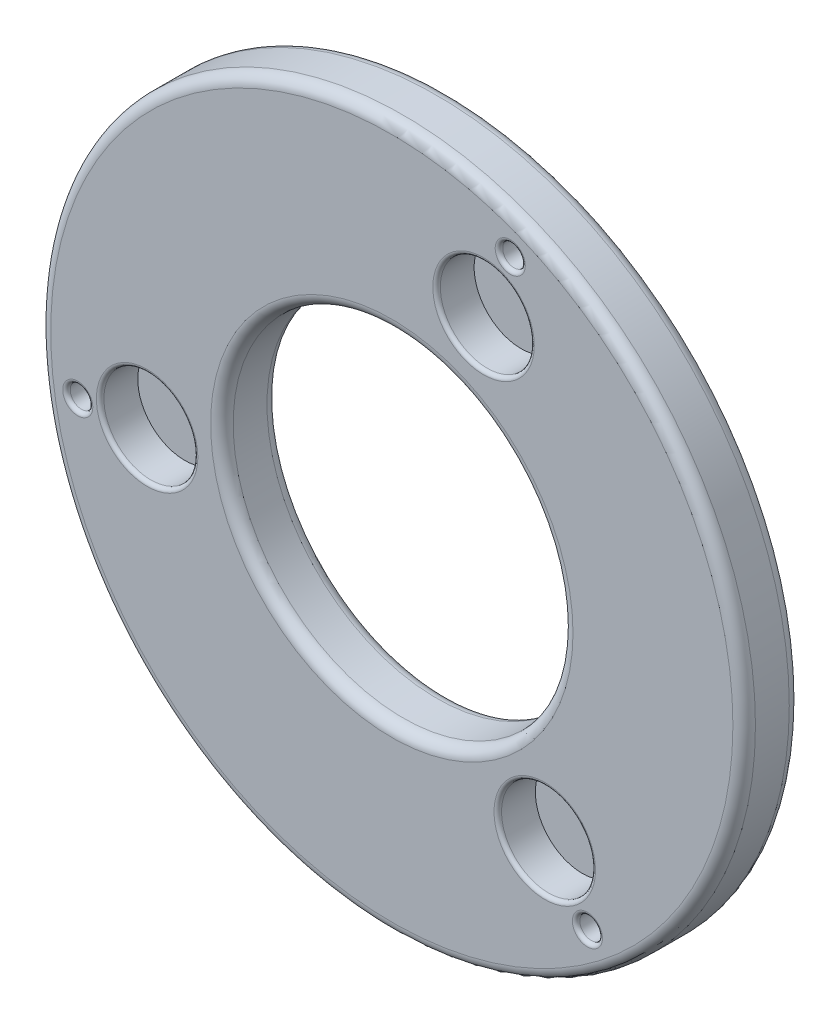
SolidWorks part; units mm, degrees
ref_plane "Front Plane" through (0, 0, 0) normal (0, 0, 1) x (1, 0, 0)
ref_plane "Top Plane" through (0, 0, 0) normal (0, 1, 0) x (1, 0, 0)
ref_plane "Right Plane" through (0, 0, 0) normal (1, 0, 0) x (0, 0, -1)
sketch "Sketch1" plane through (0, 0, 0) normal (0, 0, 1) x (1, 0, 0)
  circle A0 centre (0, 0) radius 187.5
  dimension "D1" = 375
extrude "Boss-Extrude1" add sketch "Sketch1" along normal blind 30 contours A0
sketch "Sketch3" plane through (0, 0, 30) normal (0, 0, 1) x (1, 0, 0)
  line L1 (48.8105, 122.1581) -> (-130.1972, -18.8079)
  line L2 (-130.1972, -18.8079) -> (81.3868, -103.3501)
  line L3 (81.3868, -103.3501) -> (48.8105, 122.1581)
  line L4 (63.0229, 156.5661) -> (-167.1017, -23.7037)
  line L5 (-167.1017, -23.7037) -> (104.0788, -132.8625)
  line L6 (104.0788, -132.8625) -> (63.0229, 156.5661)
  circle A0 centre (0, 0) radius 65.7743 construction
  circle A1 centre (48.8105, 122.1581) radius 25
  circle A2 centre (81.3868, -103.3501) radius 25
  circle A3 centre (-130.1972, -18.8079) radius 25
  circle A4 centre (0, 0) radius 84.3872 construction
  circle A5 centre (63.0229, 156.5661) radius 6
  circle A6 centre (104.0788, -132.8625) radius 6
  circle A7 centre (-167.1017, -23.7037) radius 6
  dimension "D1" = 50
extrude "Cut-Extrude1" cut sketch "Sketch3" against normal blind 20 contours A2 | A3 | A1
extrude "Cut-Extrude2" cut sketch "Sketch3<3>" against normal up to surface (30 mm away) contours L4 A7 L5 | L5 A6 L6 | L6 A6 L5 | L5 A7 L4 | L4 A5 L6 | L6 A5 L4 | A5 region at (63.3081, 157.2748, 30) region at (61.5965, 153.0227, 30) region at (-163.3198, -23.1672, 30) region at (-167.858, -23.811, 30) region at (104.5499, -133.4638, 30) region at (101.7233, -129.8555, 30) up to face at (187.5, 0, 0)
sketch "Sketch3<3>" plane through (0, 0, 30) normal (0, 0, 1) x (1, 0, 0) same geometry as "Sketch3"
fillet "Fillet1" radius 2 3 edges at (73.8105, 122.1581, 30) (106.3868, -103.3501, 30) (-105.1972, -18.8079, 30)
fillet "Fillet2" radius 2 6 edges at (-161.1017, -23.7037, 0) (69.0229, 156.5661, 0) (110.0788, -132.8625, 0) (69.0229, 156.5661, 30) (110.0788, -132.8625, 30) (-161.1017, -23.7037, 30)
fillet "Fillet3" radius 6 2 edges at (187.5, 0, 0) (187.5, 0, 30)
sketch "Sketch4" plane through (0, 0, 30) normal (0, 0, 1) x (1, 0, 0)
  circle A0 centre (0, 0) radius 90.4224
extrude "Cut-Extrude3" cut sketch "Sketch4" against normal up to surface (30 mm away) up to face at (181.5, 0, 0)
fillet "Fillet4" radius 6 2 edges at (90.4224, 0, 0) (90.4224, 0, 30)
